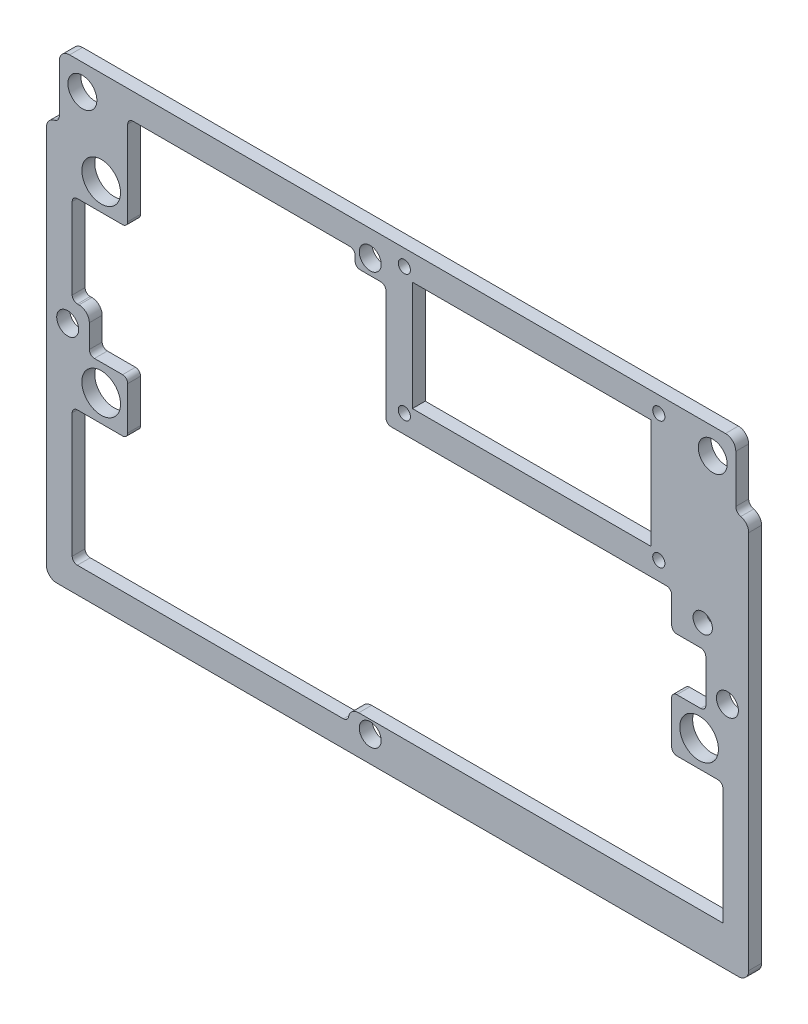
SolidWorks part; units mm, degrees
material "ABS PC"
ref_plane "Front Plane" through (0, 0, 0) normal (0, 0, 1) x (1, 0, 0)
ref_plane "Top Plane" through (0, 0, 0) normal (0, 1, 0) x (1, 0, 0)
ref_plane "Right Plane" through (0, 0, 0) normal (1, 0, 0) x (0, 0, -1)
sketch "Sketch1" plane through (0, 0, 0) normal (0, 0, 1) x (1, 0, 0)
  line L0 (94.968, 16.637) -> (-44.732, 16.637) construction
  line L1 (-61.4007, -97.663) -> (111.6368, -97.663)
  line L2 (-61.4007, -97.663) -> (-61.4007, 16.637)
  line L3 (-61.4007, 16.637) -> (111.6368, 16.637)
  line L4 (111.6368, -97.663) -> (111.6368, 16.637)
  line L5 (-61.4007, -97.663) -> (111.6368, 16.637) construction
  line L6 (-61.4007, 16.637) -> (111.6368, -97.663) construction
  point P4 (25.118, -40.513)
extrude "Boss-Extrude1" add sketch "Sketch1" along normal blind 3.175
sketch "Sketch3" plane through (0, 0, 3.175) normal (0, 0, 1) x (1, 0, 0)
  circle A0 centre (100.302, -26.543) radius 2.3813
  circle A1 centre (99.413, -51.6255) radius 4.7625
  circle A2 centre (-47.907, -51.6255) radius 4.7625
  circle A3 centre (-47.907, -6.5405) radius 4.7625
  dimension "D1" = 4.7625
  dimension "D2" = 9.525
extrude "Cut-Extrude1" cut sketch "Sketch3" against normal through all
hole_wizard "#6 Clearance Hole1" positions "Sketch5" profile "Sketch4" hole size "#6" standard "ANSI Inch" end condition through all
sketch "Sketch5" plane through (0, 0, 3.175) normal (0, 0, 1) x (1, 0, 0)
  point P0 (18.387, 10.287)
  point P3 (-56.162, -40.894)
  point P6 (106.398, -40.894)
  point P9 (18.387, -91.313)
sketch "Sketch4" plane through (18.387, 10.287, 3.175) normal (1, 0, 0) x (0, -1, 0)
  line L0 (0, 0) -> (0, 3.175)
  line L1 (0, 3.175) -> (2.1526, 3.175)
  line L2 (2.1526, 3.175) -> (2.1526, 0)
  line L5 (2.1526, 0) -> (0, 0)
  line L11 (0, -6.35) -> (0, 107.95) construction
  dimension "Thru Hole Dia." = 4.3053
  dimension "Thru Hole Depth" = 3.175
hole_wizard "#2 Clearance Hole1" positions "Sketch7" profile "Sketch6" hole size "#2" standard "ANSI Inch" end condition through all
sketch "Sketch7" plane through (0, 0, 3.175) normal (0, 0, 1) x (1, 0, 0)
  point P0 (26.788, 12.7)
  point P3 (89.488, 12.7)
  point P6 (89.488, -18.6)
  point P9 (26.788, -18.6)
sketch "Sketch6" plane through (26.788, 12.7, 3.175) normal (1, 0, 0) x (0, -1, 0)
  line L0 (0, 0) -> (0, 3.175)
  line L1 (0, 3.175) -> (1.3525, 3.175)
  line L2 (1.3525, 3.175) -> (1.3525, 0)
  line L5 (1.3525, 0) -> (0, 0)
  line L11 (0, -6.35) -> (0, 107.95) construction
  dimension "Thru Hole Dia." = 2.7051
  dimension "Thru Hole Depth" = 3.175
sketch "Sketch8" plane through (0, 0, 3.175) normal (0, 0, 1) x (1, 0, 0)
  line L9 (92.658, -23.1276) -> (22.2605, -23.1276)
  line L10 (22.2605, -23.1276) -> (22.2605, 6.5468)
  line L11 (22.2605, 6.5468) -> (14.6469, 6.5468)
  line L12 (92.658, -23.1276) -> (92.658, -32.1509)
  line L13 (28.768, 10.37) -> (28.768, -16.62)
  line L14 (28.768, -16.62) -> (87.508, -16.62)
  line L15 (87.508, -16.62) -> (87.508, 10.37)
  line L16 (87.508, 10.37) -> (28.768, 10.37)
  line L17 (28.768, 10.37) -> (28.768, -16.62)
  line L18 (28.768, -16.62) -> (87.508, -16.62)
  line L19 (87.508, -16.62) -> (87.508, 10.37)
  line L20 (87.508, 10.37) -> (28.768, 10.37)
  line L21 (92.658, -32.1509) -> (101.0704, -32.1509)
  line L22 (101.0704, -32.1509) -> (101.0704, -45.0855)
  line L23 (101.0704, -45.0855) -> (92.658, -45.0855)
  line L24 (92.658, -45.0855) -> (92.658, -58.1655)
  line L25 (92.658, -58.1655) -> (105.2868, -58.1655)
  line L26 (105.2868, -58.1655) -> (105.2868, -88.138)
  line L27 (105.2868, -88.138) -> (13.0594, -88.138)
  line L28 (13.0594, -88.138) -> (13.0594, -91.313)
  line L29 (13.0594, -91.313) -> (-55.0507, -91.313)
  line L30 (-55.0507, -91.313) -> (-55.0507, -58.1655)
  line L31 (-55.0507, -58.1655) -> (-41.367, -58.1655)
  line L32 (-41.367, -58.1655) -> (-41.367, -45.0855)
  line L33 (-41.367, -45.0855) -> (-50.8343, -45.0855)
  line L34 (-50.8343, -45.0855) -> (-50.8343, -35.5664)
  line L35 (-50.8343, -35.5664) -> (-55.0507, -35.5664)
  line L36 (-55.0507, -35.5664) -> (-55.0507, -13.0805)
  line L37 (-55.0507, -13.0805) -> (-41.367, -13.0805)
  line L38 (-41.367, -13.0805) -> (-41.367, 10.287)
  line L39 (14.6469, 6.5468) -> (14.6469, 10.287)
  line L40 (14.6469, 10.287) -> (-41.367, 10.287)
  line L43 (92.658, -45.0855) -> (109.0968, -45.0855) construction
  line L44 (111.6368, -97.663) -> (111.6368, 16.637) construction
  line L45 (-61.4007, -97.663) -> (111.6368, -97.663) construction
  line L46 (-61.4007, 16.637) -> (-61.4007, -97.663) construction
  line L47 (111.6368, 16.637) -> (-61.4007, 16.637) construction
  circle A1 centre (106.398, -40.894) radius 2.1526 construction
  circle A3 centre (18.387, -91.313) radius 2.1526 construction
  circle A8 centre (-56.162, -40.894) radius 2.1526 construction
  circle A11 centre (18.387, 10.287) radius 2.1526 construction
  circle A13 centre (26.788, -18.6) radius 1.3525 construction
  dimension "D1" = 1.27
  dimension "D10" = 1.5875
  dimension "D2" = 3.175
  dimension "D3" = 6.35
  dimension "D4" = 9.525
  dimension "D5" = 3.175
  dimension "D6" = 6.35
  dimension "D7" = 6.35
  dimension "D8" = 3.175
  dimension "D9" = 3.175
  dimension "D11" = 1.5875
  dimension "D12" = 6.35
  dimension "D13" = 3.175
  dimension "D14" = 3.175
extrude "Cut-Extrude2" cut sketch "Sketch8" against normal through all contours L19 L20 L17 L18 | L39 L40 L38 L37 L36 L35 L34 L33 L32 L31 L30 L29 L28 L27 L26 L25 L24 L23 L22 L21 L12 L9 L10 L11 region at (16.8246, -47.9652, 3.175) region at (58.138, -3.125, 3.175)
hole_wizard "#3 (0.213) Diameter Hole1" positions "3DSketch1" profile "Sketch9" hole size "#3" standard "ANSI Inch" end condition through all
sketch3d "3DSketch1"
  line L0 (18.387, 10.287, 0) -> (18.387, 10.287, 3.175) construction
  line L1 (-56.162, -40.894, 0) -> (-56.162, -40.894, 3.175) construction
  line L2 (18.387, -91.313, 0) -> (18.387, -91.313, 3.175) construction
  line L3 (106.398, -40.894, 0) -> (106.398, -40.894, 3.175) construction
  point P0 (18.387, 10.287, 3.175)
  point P5 (-56.162, -40.894, 3.175)
  point P9 (18.387, -91.313, 3.175)
  point P13 (106.398, -40.894, 3.175)
sketch "Sketch9" plane through (18.387, 10.287, 3.175) normal (1, 0, 0) x (0, -1, 0)
  line L0 (0, 0) -> (0, 3.175)
  line L1 (0, 3.175) -> (2.7051, 3.175)
  line L2 (2.7051, 3.175) -> (2.7051, 0)
  line L5 (2.7051, 0) -> (0, 0)
  line L11 (0, -6.35) -> (0, 107.95) construction
  dimension "Thru Hole Dia." = 5.4102
  dimension "Thru Hole Depth" = 3.175
hole_wizard "Ø3.0 (3) Diameter Hole1" positions "Sketch11" profile "Sketch10" hole size "Ø3.0" standard "ANSI Metric" end condition through all
sketch "Sketch11" plane through (0, 0, 3.175) normal (0, 0, 1) x (1, 0, 0)
  point P0 (26.788, 12.7)
  point P3 (89.488, 12.7)
  point P6 (89.488, -18.6)
  point P9 (26.788, -18.6)
sketch "Sketch10" plane through (26.788, 12.7, 3.175) normal (1, 0, 0) x (0, -1, 0)
  line L0 (0, 0) -> (0, 3.175)
  line L1 (0, 3.175) -> (1.5, 3.175)
  line L2 (1.5, 3.175) -> (1.5, 0)
  line L5 (1.5, 0) -> (0, 0)
  line L11 (0, -6.35) -> (0, 107.95) construction
  dimension "Thru Hole Dia." = 3
  dimension "Thru Hole Depth" = 3.175
fillet "Fillet1" radius 1.27 21 edges at (-41.367, 10.287, 1.5875) (-41.367, -13.0805, 1.5875) (-55.0507, -13.0805, 1.5875) (-55.0507, -35.5664, 1.5875) (-50.8343, -45.0855, 1.5875) (-41.367, -45.0855, 1.5875) (-41.367, -58.1655, 1.5875) (-55.0507, -58.1655, 1.5875) (-55.0507, -91.313, 1.5875) (13.0594, -91.313, 1.5875) (105.2868, -58.1655, 1.5875) (92.658, -58.1655, 1.5875) (92.658, -45.0855, 1.5875) (101.0704, -45.0855, 1.5875) (101.0704, -32.1509, 1.5875) (92.658, -32.1509, 1.5875) (92.658, -23.1276, 1.5875) (22.2605, -23.1276, 1.5875) (14.6469, 6.5468, 1.5875) (22.2605, 6.5468, 1.5875) (14.6469, 10.287, 1.5875)
fillet "Fillet2" radius 2.54 6 edges at (13.0594, -88.138, 1.5875) (-50.8343, -35.5664, 1.5875) (111.6368, 16.637, 1.5875) (111.6368, -97.663, 1.5875) (-61.4007, -97.663, 1.5875) (-61.4007, 16.637, 1.5875)
hole_wizard "1/4 Clearance Hole1" positions "Sketch12" profile "Sketch13" hole size "1/4" standard "ANSI Inch" end condition up to next
sketch "Sketch12" plane through (0, 0, 0) normal (0, 0, -1) x (-1, 0, 0)
  point P0 (-102.7785, 10.287)
  point P2 (52.5425, 10.287)
sketch "Sketch13" plane through (102.7785, 10.287, 0) normal (1, 0, 0) x (0, 1, 0)
  line L0 (0, 0) -> (0, 3.175)
  line L1 (0, 3.175) -> (3.5712, 3.175)
  line L2 (3.5712, 3.175) -> (3.5712, 0)
  line L5 (3.5712, 0) -> (0, 0)
  line L11 (0, -6.35) -> (0, 107.95) construction
  dimension "Thru Hole Dia." = 7.1425
  dimension "Thru Hole Depth" = 3.175
sketch "Sketch14" plane through (0, 0, 0) normal (0, 0, -1) x (-1, 0, 0)
  line L0 (-111.6368, -95.123) -> (-111.6368, 14.097) construction
  line L1 (-111.6368, 0.762) -> (-108.4618, 0.762)
  line L2 (-111.6368, 0.762) -> (-111.6368, 16.637)
  line L3 (-111.6368, 16.637) -> (-108.4618, 16.637)
  line L4 (-108.4618, 0.762) -> (-108.4618, 16.637)
  line L5 (-109.0967, 16.637) -> (58.8607, 16.637) construction
  line L6 (-25.118, -97.663) -> (-25.118, 16.637) construction
  line L7 (58.8607, -97.663) -> (-109.0967, -97.663) construction
  line L8 (58.2257, 0.762) -> (58.2257, 16.637)
  line L9 (61.4008, 16.637) -> (58.2257, 16.637)
  line L10 (61.4008, 0.762) -> (61.4008, 16.637)
  line L11 (61.4008, 0.762) -> (58.2257, 0.762)
  dimension "D1" = 3.175
  dimension "D2" = 15.875
extrude "Cut-Extrude3" cut sketch "Sketch14" against normal up to next
fillet "Fillet3" radius 1.5875 2 edges at (-58.2257, 0.762, 1.5875) (108.4618, 0.762, 1.5875)
fillet "Fillet4" radius 2.54 4 edges at (111.6368, 0.762, 1.5875) (108.4617, 16.637, 1.5875) (-58.2257, 16.637, 1.5875) (-61.4008, 0.762, 1.5875)
